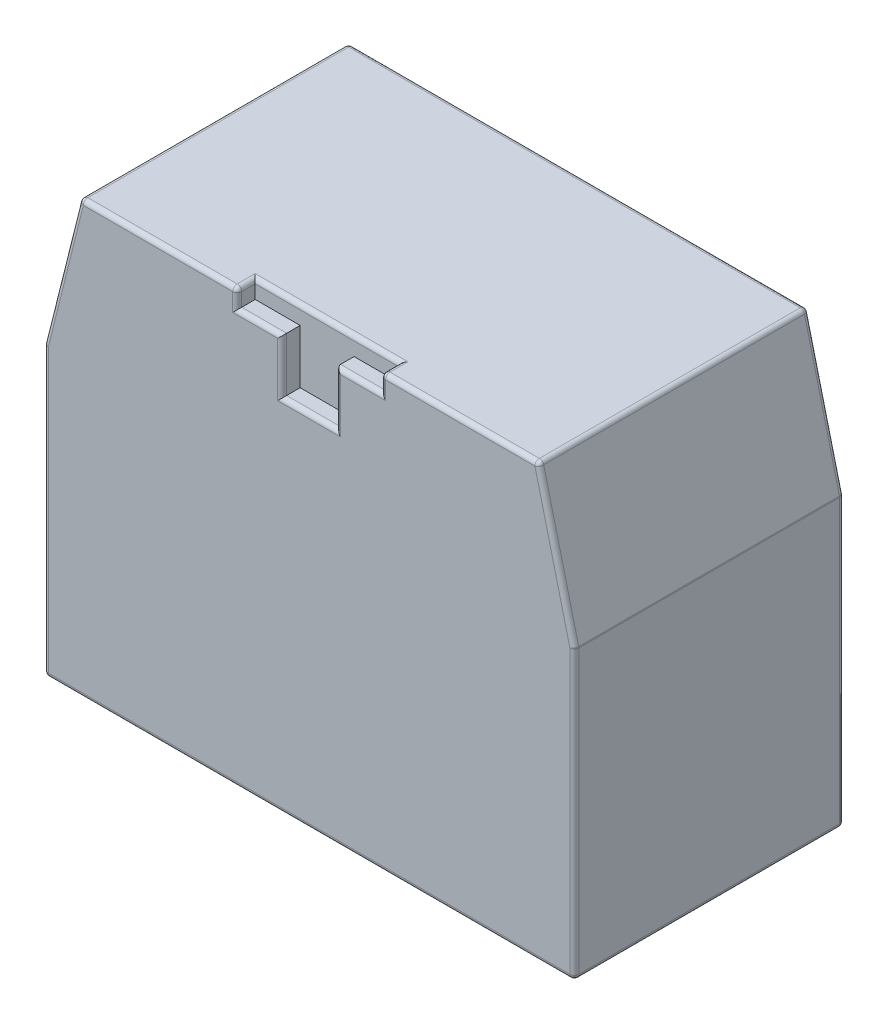
SolidWorks part; units mm, degrees
ref_plane "Plan de face" through (0, 0, 0) normal (0, 0, 1) x (1, 0, 0)
ref_plane "Plan de dessus" through (0, 0, 0) normal (0, 1, 0) x (1, 0, 0)
ref_plane "Plan de droite" through (0, 0, 0) normal (1, 0, 0) x (0, 0, -1)
sketch "Esquisse1" plane through (0, 0, 0) normal (0, 0, 1) x (1, 0, 0)
  line L0 (0, 16) -> (2, 24)
  line L1 (0, 0) -> (29.5, 0)
  line L2 (0, 0) -> (0, 16)
  line L3 (2, 24) -> (27.5, 24)
  line L4 (29.5, 0) -> (29.5, 16)
  line L5 (14.75, 24) -> (14.75, 0) construction
  line L6 (27.5, 24) -> (29.5, 16)
  dimension "D1" = 29.5
  dimension "D2" = 24
  dimension "D3" = 8
extrude "Boss.-Extru.1" add sketch "Esquisse1" along normal blind 15
sketch "Esquisse2" plane through (0, 0, 15) normal (0, 0, 1) x (1, 0, 0)
  line L0 (14.75, 24) -> (14.75, 20) construction
  line L1 (27.5, 24) -> (2, 24) construction
  line L2 (16.25, 23) -> (18.75, 23)
  line L3 (10.75, 24) -> (18.75, 24)
  line L4 (10.75, 24) -> (10.75, 23)
  line L5 (10.75, 23) -> (13.25, 23)
  line L6 (18.75, 24) -> (18.75, 23)
  line L8 (13.25, 23) -> (13.25, 20)
  line L9 (13.25, 20) -> (16.25, 20)
  line L10 (16.25, 23) -> (16.25, 20)
  point P12 (14.75, 23)
  dimension "D1" = 3
  dimension "D2" = 8
  dimension "D3" = 1
  dimension "D4" = 3
extrude "Enlèv. mat.-Extru.1" cut sketch "Esquisse2" against normal blind 1
sketch "Esquisse3" plane through (0, 0, 0) normal (0, -1, 0) x (1, 0, 0)
  line L0 (14.75, 15) -> (14.75, 0) construction
  line L1 (0, 15) -> (29.5, 15) construction
  line L2 (0, 0) -> (29.5, 0) construction
  line L3 (0, 15) -> (0, 0) construction
  line L4 (24.0486, 8.4062) -> (22.9255, 8.4062)
  line L5 (2, 8) -> (2, 4)
  line L6 (2, 4) -> (8, 4)
  line L7 (8, 8) -> (8, 4)
  line L8 (24.0486, 7.5729) -> (22.9255, 7.5729)
  line L9 (24.8456, 7.5729) -> (24.8456, 6.3955)
  line L10 (5.4514, 7.5729) -> (5.4514, 6.3955)
  line L11 (4.6544, 9.5112) -> (5.4514, 9.5112)
  line L12 (4.6544, 9.5112) -> (4.6544, 8.4062)
  line L13 (4.6544, 6.3955) -> (5.4514, 6.3955)
  line L14 (5.4514, 9.5112) -> (5.4514, 8.4062)
  line L15 (3.4045, 8.4062) -> (4.6544, 8.4062)
  line L16 (3.4045, 8.4062) -> (3.4045, 7.5729)
  line L17 (3.4045, 7.5729) -> (4.6544, 7.5729)
  line L18 (6.5745, 8.4062) -> (6.5745, 7.5729)
  line L19 (4.6544, 7.5729) -> (4.6544, 6.3955)
  line L20 (5.4514, 7.5729) -> (6.5745, 7.5729)
  line L21 (5.4514, 8.4062) -> (6.5745, 8.4062)
  line L22 (22.9255, 8.4062) -> (22.9255, 7.5729)
  line L23 (26.0955, 7.5729) -> (24.8456, 7.5729)
  line L24 (26.0955, 8.4062) -> (26.0955, 7.5729)
  line L25 (26.0955, 8.4062) -> (24.8456, 8.4062)
  line L26 (24.0486, 9.5112) -> (24.0486, 8.4062)
  line L27 (24.8456, 6.3955) -> (24.0486, 6.3955)
  line L28 (24.8456, 9.5112) -> (24.8456, 8.4062)
  line L29 (24.8456, 9.5112) -> (24.0486, 9.5112)
  line L30 (24.0486, 7.5729) -> (24.0486, 6.3955)
  line L31 (21.5, 8) -> (21.5, 4)
  line L32 (27.5, 4) -> (21.5, 4)
  line L33 (27.5, 8) -> (27.5, 4)
  line L34 (15.1281, 13.2806) -> (14.3311, 13.2806)
  line L36 (13.208, 12.1756) -> (13.208, 11.3423)
  line L37 (14.3311, 11.3423) -> (13.208, 11.3423)
  line L39 (15.1281, 10.1649) -> (14.3311, 10.1649)
  line L40 (14.3311, 11.3423) -> (14.3311, 10.1649)
  line L41 (15.1281, 11.3423) -> (15.1281, 10.1649)
  line L42 (16.3781, 11.3423) -> (15.1281, 11.3423)
  line L43 (14.3311, 13.2806) -> (14.3311, 12.1756)
  line L44 (15.1281, 13.2806) -> (15.1281, 12.1756)
  line L46 (14.3311, 12.1756) -> (13.208, 12.1756)
  line L47 (16.3781, 12.1756) -> (16.3781, 11.3423)
  line L48 (16.3781, 12.1756) -> (15.1281, 12.1756)
  arc A0 (8, 8) -> (2, 8) centre (5, 8) ccw
  circle A1 centre (24.5, 8) radius 2.5
  circle A2 centre (5, 8) radius 2.5
  arc A3 (21.5, 8) -> (27.5, 8) centre (24.5, 8) cw
  circle A5 centre (14.7825, 11.7694) radius 2.5
  circle A6 centre (14.7825, 11.7694) radius 3
  dimension "D5" = 5
  dimension "D1" = 4
  dimension "D2" = 6
  dimension "D3" = 4
  dimension "D4" = 2
extrude "Enlèv. mat.-Extru.2" cut sketch "Esquisse3" against normal blind 2 contours L7 A0 L5 L6 A2 | L21 L14 L11 L12 L15 L16 L17 L19 L13 L10 L20 L18 | A3 L31 L32 L33 A1 | L8 L30 L27 L9 L23 L24 L25 L28 L29 L26 L4 L22 | A6 L0 A5 | L0 A6 A5 | L0 L34 L43 L46 L36 L37 L40 L39 | L34 L0 L39 L41 L42 L47 L48 L44 region at (16.845, 0, 13.8544) region at (14.6831, 0, 14.5192) region at (15.321, 0, 11.7397) region at (14.2186, 0, 11.7379) region at (24.4846, 0, 7.9694) region at (5, 0, 10.9078) region at (5.0154, 0, 7.9694) region at (24.5, 0, 10.9078)
fillet "Congé1" radius 0.25 53 edges at (27.5, 1, 4) (21.5, 1, 4) (27.5, 2, 6) (24.5, 2, 4) (21.5, 2, 6) (24.5, 2, 11) (2, 1, 4) (8, 1, 4) (5, 2, 4) (2, 2, 6) (5, 2, 11) (8, 2, 6) (29.5, 16, 7.5) (29.5, 8, 0) (28.5, 20, 0) (14.75, 24, 0) (27.5, 24, 7.5) (18.75, 24, 14.5) (14.75, 24, 14) (10.75, 24, 14.5) (2, 24, 7.5) (1, 20, 0) (0, 16, 7.5) (0, 8, 0) (13.25, 21.5, 15) (14.75, 20, 15) (16.25, 21.5, 15) (17.5, 23, 15) (18.75, 23.5, 15) (23.125, 24, 15) (28.5, 20, 15) (29.5, 8, 15) (0, 8, 15) (1, 20, 15) (6.375, 24, 15) (10.75, 23.5, 15) (12, 23, 15) (21.5, 0, 6) (24.5, 0, 4) (27.5, 0, 6) (24.5, 0, 11) (5, 0, 11) (2, 0, 6) (5, 0, 4) (8, 0, 6) (0, 0, 7.5) (14.75, 0, 15) (29.5, 0, 7.5) (14.75, 0, 0) (24.5, 0, 5.5) (5, 0, 5.5) (14.7825, 0, 8.7694) (14.7825, 0, 9.2694)
